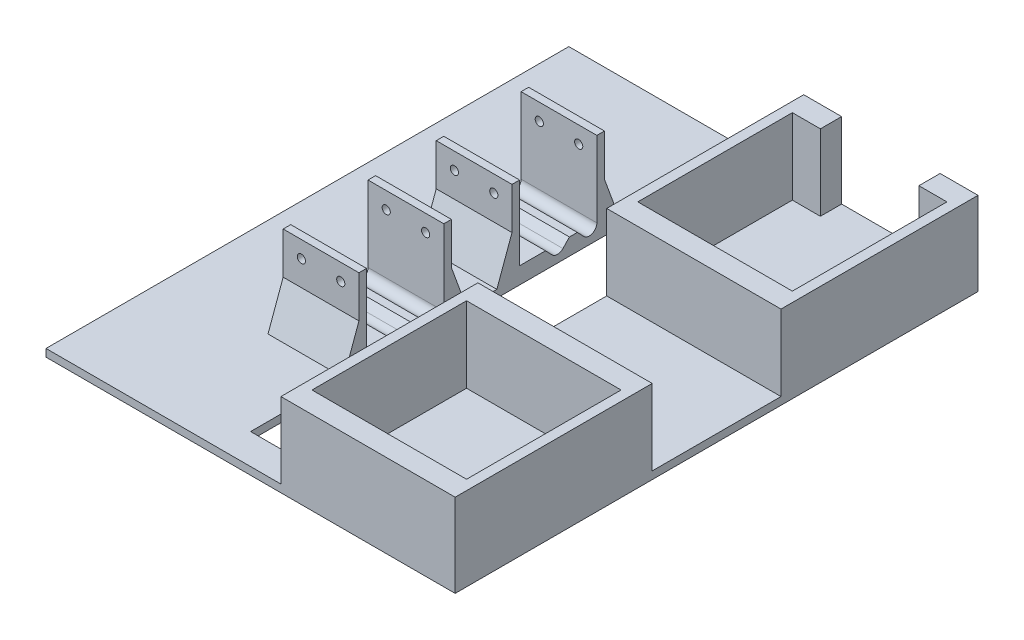
SolidWorks part; units mm, degrees
ref_plane "Front Plane" through (0, 0, 0) normal (0, 0, 1) x (1, 0, 0)
ref_plane "Top Plane" through (0, 0, 0) normal (0, 1, 0) x (1, 0, 0)
ref_plane "Right Plane" through (0, 0, 0) normal (1, 0, 0) x (0, 0, -1)
sketch "Sketch1" plane through (0, 0, 0) normal (0, 1, 0) x (1, 0, 0)
  line L1 (0, 0) -> (115, 0)
  line L2 (0, 0) -> (0, 345)
  line L3 (0, 345) -> (115, 345)
  line L5 (155, 345) -> (270, 345)
  line L7 (155, 0) -> (270, 0)
  line L8 (270, 345) -> (270, 0)
  line L9 (115, 345) -> (155, 345)
  line L11 (115, 325) -> (155, 325)
  line L13 (115, 20) -> (155, 20)
  line L17 (155, 325) -> (155, 20)
  line L18 (115, 20) -> (115, 325)
  line L20 (115, 345) -> (115, 325) construction
  line L21 (115, 20) -> (115, 0) construction
  line L22 (115, 0) -> (155, 0)
  dimension "D1" = 345
  dimension "D2" = 270
  dimension "D3" = 40
  dimension "D4" = 20
  dimension "D5" = 20
extrude "Boss-Extrude1" add sketch "Sketch1" along normal blind 5
sketch "Sketch2" plane through (0, 5, 0) normal (0, 1, 0) x (1, 0, 0)
  line L1 (65, 253.5) -> (115, 253.5)
  line L2 (65, 253.5) -> (65, 248.5)
  line L3 (65, 248.5) -> (115, 248.5)
  line L4 (115, 253.5) -> (115, 248.5)
  line L5 (65, 197.5) -> (115, 197.5)
  line L6 (65, 197.5) -> (65, 192.5)
  line L7 (65, 192.5) -> (115, 192.5)
  line L8 (115, 197.5) -> (115, 192.5)
  line L9 (115, 325) -> (115, 20) construction
  line L10 (0, 172.5) -> (270, 172.5) construction
  line L12 (65, 152.5) -> (115, 152.5)
  line L13 (115, 147.5) -> (115, 152.5)
  line L14 (65, 147.5) -> (115, 147.5)
  line L15 (65, 147.5) -> (65, 152.5)
  line L16 (65, 96.5) -> (115, 96.5)
  line L17 (115, 91.5) -> (115, 96.5)
  line L18 (65, 91.5) -> (115, 91.5)
  line L19 (65, 91.5) -> (65, 96.5)
  line L21 (270, 0) -> (270, 345) construction
  line L22 (0, 345) -> (0, 0) construction
  point P12 (270, 172.5)
  point P22 (270, 172.5)
  point P23 (0, 172.5)
  point P25 (0, 172.5)
  dimension "D1" = 5
  dimension "D2" = 51
  dimension "D3" = 50
  dimension "D4" = 40
extrude "Boss-Extrude2" add sketch "Sketch2" along normal blind 55
chamfer "Chamfer1" distance 10 angle 70 4 edges at (90, 5, -91.5) (90, 5, -152.5) (90, 5, -192.5) (90, 5, -253.5) first distance on face at (135, 5, -172.5)
sketch "Sketch4" plane through (115, 0, 0) normal (1, 0, 0) x (0, 0, -1)
  line L0 (147.5, 60) -> (147.5, 5) construction
  line L1 (96.5, 5) -> (147.5, 5)
  line L2 (96.5, 5) -> (96.5, 11)
  line L3 (96.5, 11) -> (147.5, 11)
  line L4 (147.5, 5) -> (147.5, 11)
  line L5 (142.5, 5) -> (142.5, 11) construction
  line L6 (134.601, 11) -> (138.4184, 7.112)
  line L7 (134.601, 11) -> (137.601, 11)
  line L8 (147.5, 10) -> (96.5, 10) construction
  line L9 (125.1038, 6.534) -> (129.399, 11)
  line L10 (129.399, 11) -> (126.399, 11)
  line L11 (117.8962, 6.534) -> (113.601, 11)
  line L12 (113.601, 11) -> (116.601, 11)
  line L13 (172.5, 5) -> (172.5, 54.1934) construction
  line L14 (182.5, 5) -> (162.5, 5) construction
  line L19 (197.5, 5) -> (248.5, 5)
  line L20 (197.5, 5) -> (197.5, 11)
  line L21 (197.5, 11) -> (248.5, 11)
  line L22 (248.5, 5) -> (248.5, 11)
  line L23 (243.5, 5) -> (243.5, 11) construction
  line L24 (235.601, 11) -> (239.8962, 6.534)
  line L25 (235.601, 11) -> (238.601, 11)
  line L26 (248.5, 10) -> (197.5, 10) construction
  line L27 (226.1038, 6.534) -> (230.399, 11)
  line L28 (230.399, 11) -> (227.399, 11)
  line L29 (218.8962, 6.534) -> (214.601, 11)
  line L30 (214.601, 11) -> (217.601, 11)
  line L31 (248.5, 60) -> (248.5, 5) construction
  line L32 (197.5, 60) -> (197.5, 5) construction
  circle A0 centre (142.5, 10) radius 5
  circle A1 centre (121.5, 10) radius 5
  circle A4 centre (243.5, 10) radius 5
  circle A5 centre (222.5, 10) radius 5
  point P49 (248.5, 7.5177)
  point P52 (248.5, 5)
  point P53 (199.469, 5)
  point P54 (197.5, 11)
  line M10 (248.5, 5) -> (197.5, 5)
  line M11 (197.5, 5) -> (197.5, 60)
  line M20 (147.5, 5) -> (96.5, 5)
  line M21 (96.5, 5) -> (96.5, 60)
  dimension "D2" = 10
  dimension "D5" = 10
  dimension "D10" = 10
  dimension "D16" = 10
  dimension "D1" = 6
  dimension "D3" = 6
  dimension "D4" = 3
  dimension "D6" = 26
  dimension "D7" = 3
  dimension "D8" = 3
  dimension "D9" = 6
  dimension "D11" = 6
  dimension "D12" = 3
  dimension "D13" = 3
  dimension "D14" = 3
  dimension "D15" = 26
extrude "Boss-Extrude3" add sketch "Sketch4" against normal blind 50 contours A1 L11 L3 M21 M20 | A1 L1 A0 L6 L3 L9 | A0 L4 M20 | A5 L29 L21 M11 M10 | A5 L19 A4 L24 L21 L27 | A4 L22 M10 region at (115, 7.8434, -106.625) region at (115, 7.4388, -132.0131) region at (115, 6.1168, -146.3832) region at (115, 7.8434, -207.625) region at (115, 7.4367, -233) region at (115, 6.1168, -247.3832)
sketch "Sketch3" plane through (0, 0, -248.5) normal (0, 0, 1) x (1, 0, 0)
  line L0 (90, 5) -> (90, 60) construction
  line L1 (65, 5) -> (115, 5) construction
  line L2 (65, 60) -> (115, 60) construction
  line L3 (65, 5) -> (115, 5) construction
  circle A0 centre (77, 49) radius 2.7
  circle A1 centre (103, 49) radius 2.7
  dimension "D3" = 5.4
  dimension "D1" = 13
  dimension "D2" = 44
extrude "Cut-Extrude1" cut sketch "Sketch3" against normal through all both and the other way through all
sketch "Sketch5" plane through (0, 5, 0) normal (0, 1, 0) x (1, 0, 0)
  line L0 (155, 20) -> (155, 325) construction
  line L1 (270, 0) -> (155, 0)
  line L2 (270, 0) -> (270, 130)
  line L3 (270, 130) -> (155, 130)
  line L4 (155, 0) -> (155, 130)
  line L5 (270, 172.5) -> (155, 172.5) construction
  line L6 (161.5, 116) -> (263.5, 116)
  line L7 (161.5, 116) -> (161.5, 14)
  line L8 (161.5, 14) -> (263.5, 14)
  line L9 (263.5, 116) -> (263.5, 14)
  line L10 (270, 0) -> (270, 345) construction
  line L11 (263.5, 229) -> (263.5, 331)
  line L12 (161.5, 331) -> (263.5, 331)
  line L13 (161.5, 229) -> (161.5, 331)
  line L14 (161.5, 229) -> (263.5, 229)
  line L15 (155, 345) -> (155, 215)
  line L16 (270, 215) -> (155, 215)
  line L17 (270, 345) -> (270, 215)
  line L18 (270, 345) -> (155, 345)
  dimension "D1" = 115
  dimension "D2" = 130
  dimension "D3" = 14
  dimension "D4" = 14
  dimension "D5" = 6.5
  dimension "D6" = 6.5
extrude "Boss-Extrude4" add sketch "Sketch5" along normal blind 50
sketch "Sketch6" plane through (0, 0, -345) normal (0, 0, -1) x (-1, 0, 0)
  line L0 (-270, 55) -> (-155, 55) construction
  line L1 (-180, 5) -> (-245, 5)
  line L2 (-180, 5) -> (-180, 55)
  line L3 (-180, 55) -> (-245, 55)
  line L4 (-245, 5) -> (-245, 55)
  line L5 (-155, 55) -> (-155, 5) construction
  line L6 (-270, 55) -> (-270, 0) construction
  dimension "D1" = 25
  dimension "D2" = 25
extrude "Cut-Extrude2" cut sketch "Sketch6" against normal blind 50 and the other way through all
